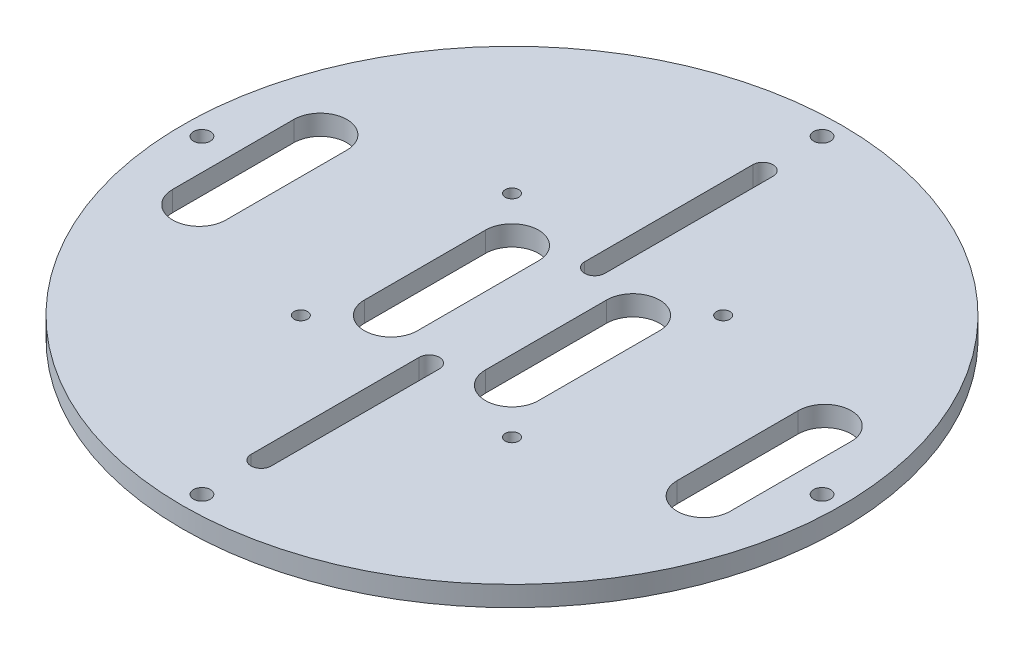
SolidWorks part; units mm, degrees
ref_plane "前视" through (0, 0, 0) normal (0, 0, 1) x (1, 0, 0)
ref_plane "上视" through (0, 0, 0) normal (0, 1, 0) x (1, 0, 0)
ref_plane "右视" through (0, 0, 0) normal (1, 0, 0) x (0, 0, -1)
sketch "草图1" plane through (0, 0, 0) normal (0, 1, 0) x (1, 0, 0)
  circle A0 centre (0, 0) radius 49
  dimension "D1" = 98
extrude "凸台-拉伸1" add sketch "草图1" along normal blind 3
sketch "草图6" plane through (0, 3, 0) normal (0, 1, 0) x (1, 0, 0)
  line L0 (0, 12.3) -> (0, 37.3) construction
  line L1 (-1.5, 12.3) -> (-1.5, 37.3)
  line L2 (1.5, 12.3) -> (1.5, 37.3)
  arc A0 (-1.5, 12.3) -> (1.5, 12.3) centre (0, 12.3) ccw
  arc A1 (1.5, 37.3) -> (-1.5, 37.3) centre (0, 37.3) ccw
  point P3 (0, 24.8)
  dimension "D1" = 25
  dimension "D2" = 12.3
extrude "切除-拉伸1" cut sketch "草图6" against normal through all
pattern_circular "阵列(圆周)2" count 2 over 360 about axis through (0, 3, 0) along (0, -1, 0) of "切除-拉伸1"
sketch "草图7" plane through (0, 3, 0) normal (0, 1, 0) x (1, 0, 0)
  line L0 (-51.2516, 0) -> (52.7908, 0) construction
  line L1 (-17.8863, 15.7) -> (-13.3805, 15.7) construction
  line L2 (-15.7, 17.8338) -> (-15.7, 13.4893) construction
  dimension "D1" = 15.7
  dimension "D2" = 15.7
sketch "草图8" plane through (0, 3, 0) normal (0, 1, 0) x (1, 0, 0)
  line L0 (-17.8863, 15.7) -> (-13.3805, 15.7) construction
  circle A0 centre (-15.7, 15.7) radius 1
  dimension "D1" = 2
sketch "草图9" plane through (0, 3, 0) normal (0, 1, 0) x (1, 0, 0)
  line L0 (-9, 26.2025) -> (-9, -24.6699) construction
  line L1 (-9, -9) -> (-9, 9) construction
  line L2 (-12.95, -9) -> (-12.95, 9)
  line L3 (-5.05, -9) -> (-5.05, 9)
  line L4 (-51.2516, 0) -> (52.7908, 0) construction
  arc A0 (-12.95, -9) -> (-5.05, -9) centre (-9, -9) ccw
  arc A1 (-5.05, 9) -> (-12.95, 9) centre (-9, 9) ccw
  point P4 (-9, 0)
extrude "切除-拉伸3" cut sketch "草图9" against normal through all
pattern_linear "阵列(线性)1" count 2 spacing 28.5 along (-1, 0, 0) of "切除-拉伸3"
pattern_circular "阵列(圆周)5" count 2 over 360 about axis through (0, 3, 0) along (0, -1, 0) of "阵列(线性)1", "切除-拉伸3"
sketch "草图14" plane through (0, 3, 0) normal (0, 1, 0) x (1, 0, 0)
  line L0 (0, 54.6999) -> (0, -58.67) construction
  circle A0 centre (0, 46.1) radius 1.25
  dimension "D1" = 46.1
extrude "切除-拉伸4" cut sketch "草图14" against normal through all
pattern_circular "阵列(圆周)6" count 4 over 360 about axis through (0, 3, 0) along (0, -1, 0) of "切除-拉伸4"
sketch "草图15" plane through (0, 3, 0) normal (0, 1, 0) x (1, 0, 0)
  line L0 (5.1524, -24.8) -> (-5.5286, -24.8) construction
  line L1 (-51.2516, 0) -> (52.7908, 0) construction
  dimension "D1" = 24.8
sketch "草图16" plane through (0, 3, 0) normal (0, 1, 0) x (1, 0, 0)
  line L0 (0, 0) -> (-15.7936, 15.7936) construction
  line L1 (-15.7936, 15.7936) -> (-16.8429, 16.8429) construction
  line L2 (-51.2516, 0) -> (52.7908, 0) construction
  dimension "D1" = 45
extrude "切除-拉伸5" cut sketch "草图8" against normal through all
pattern_circular "阵列(圆周)7" count 4 over 360 about axis through (0, 3, 0) along (0, -1, 0) of "切除-拉伸5"
